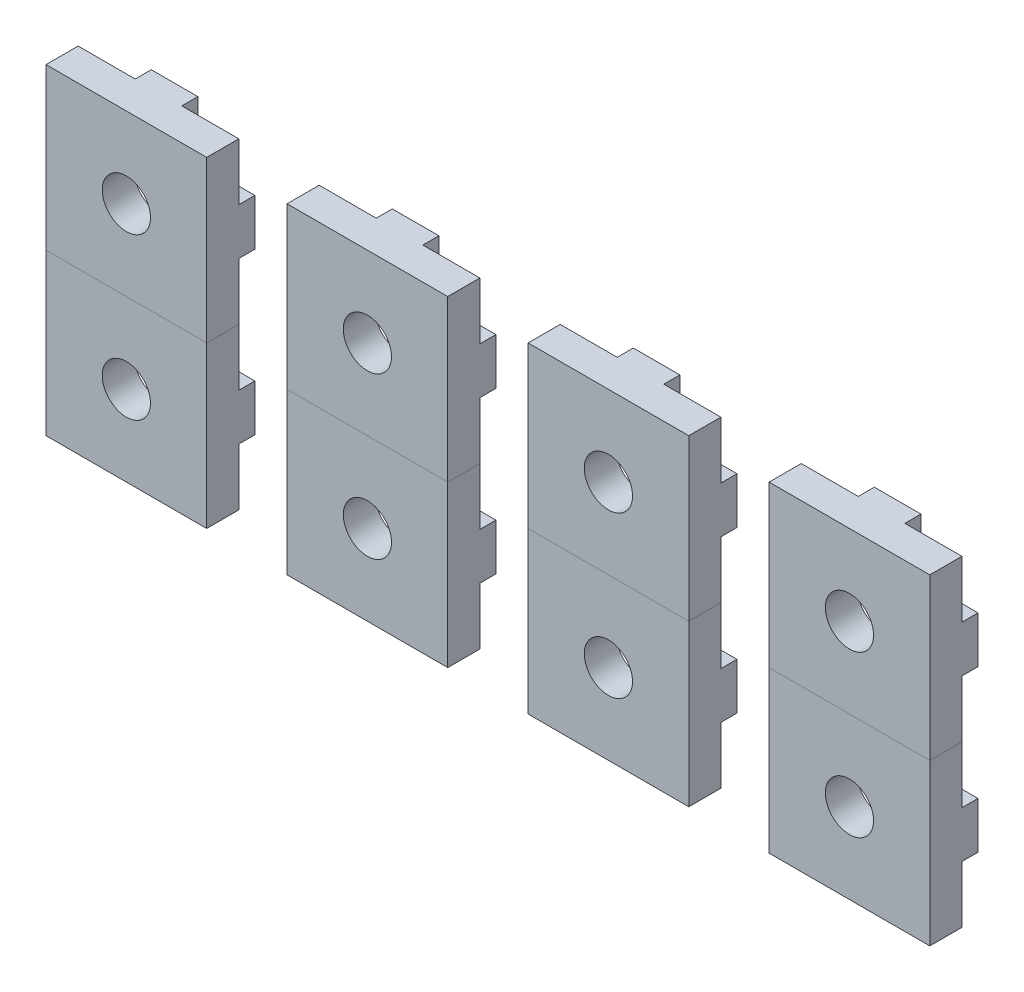
SolidWorks part; units mm, degrees
note: '?' marks a value the reader was unsure of.
ref_plane "Front Plane" through (0, 0, 0) normal (0, 0, 1) x (1, 0, 0)
ref_plane "Top Plane" through (0, 0, 0) normal (0, 1, 0) x (1, 0, 0)
ref_plane "Right Plane" through (0, 0, 0) normal (1, 0, 0) x (0, 0, -1)
ref_axis "Axis1" through (0, 0, -1.2) along (0, 0, 1)?
sketch "Sketch1" plane through (0, 0, 0) normal (0, 0, 1) x (1, 0, 0)
  line L1 (-5, -5) -> (5, -5)
  line L2 (-5, -5) -> (-5, 5)
  line L3 (-5, 5) -> (5, 5)
  line L4 (5, -5) -> (5, 5)
  line L5 (-5, -5) -> (5, 5) construction
  line L6 (-5, 5) -> (5, -5) construction
  circle A0 centre (0, 0) radius 1.5
  point P0 (0, 0)
  dimension "D3" = 3
  dimension "D1" = 10
  dimension "D2" = 10
extrude "Main" add sketch "Sketch1" along normal blind 2
sketch "Sketch2" plane through (0, 0, 0) normal (0, 0, -1) x (-1, 0, 0)
  line L0 (-5, 1.45) -> (-3.9, 1.45)
  line L1 (-5, -5) -> (-5, 5) construction
  line L2 (-3.9, 1.45) -> (-3.9, 3)
  line L3 (-3.9, -1.45) -> (-5, -1.45)
  line L4 (-5, 1.45) -> (-5, -1.45)
  line L5 (-3.9, 3) -> (-2.1, 0.95)
  line L6 (-2.1, 0.95) -> (-2.1, -0.95)
  line L7 (-2.1, -0.95) -> (-3.9, -3)
  line L8 (-3.9, -3) -> (-3.9, -1.45)
  line L9 (-5, 5) -> (5, 5) construction
  point P5 (-2.1, 0)
  dimension "D1" = 2.9
  dimension "D2" = 1.1
  dimension "D3" = 1.9
  dimension "D4" = 2.1
  dimension "D5" = 2
extrude "AntiRotationSystem" add sketch "Sketch2" along normal blind 1
pattern_circular "CirPattern1" count 4 over 360 about axis through (0, 0, 0) along (0, 0, 1) of "AntiRotationSystem"
pattern_linear "LPattern1" count 2 spacing 10 along (0, -1, 0) of bodies 103
pattern_linear "LPattern2" count 4 spacing 15 along (-1, 0, 0) of bodies 107 103
